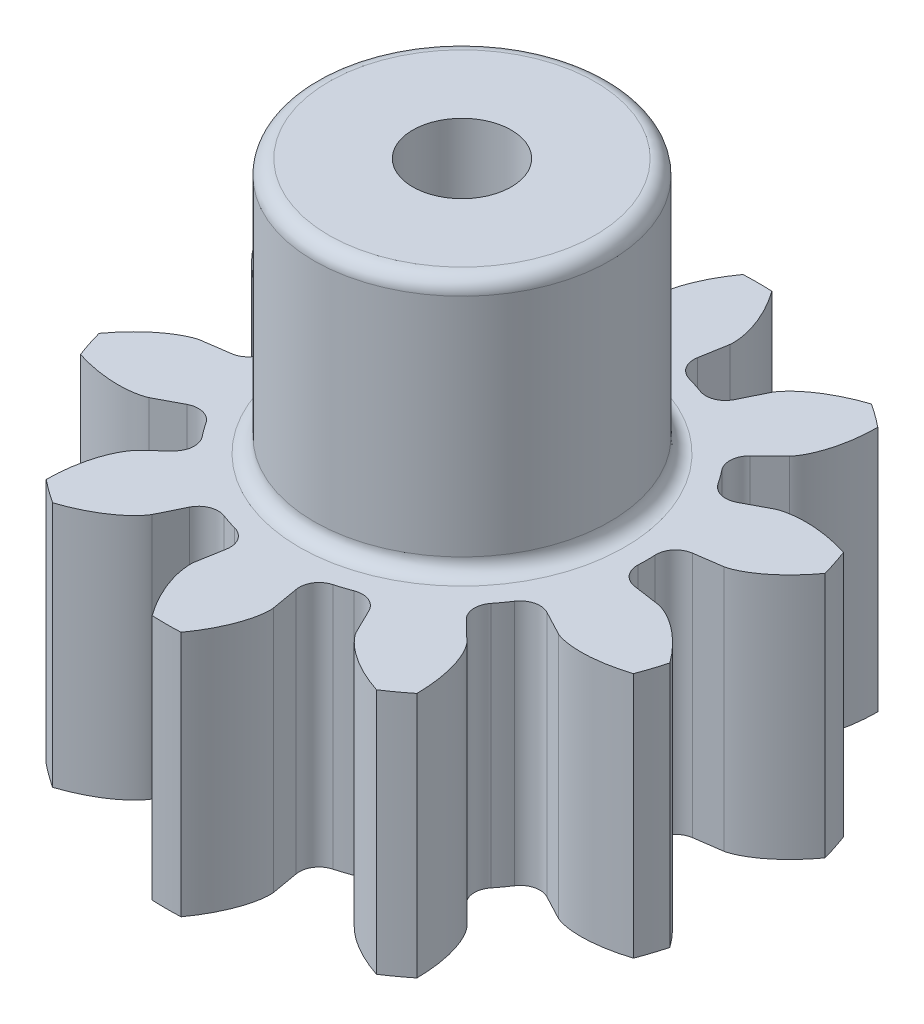
SolidWorks part; units mm, degrees
ref_plane "Front Plane" through (0, 0, 0) normal (0, 0, 1) x (1, 0, 0)
ref_plane "Top Plane" through (0, 0, 0) normal (0, 1, 0) x (1, 0, 0)
ref_plane "Right Plane" through (0, 0, 0) normal (1, 0, 0) x (0, 0, -1)
sketch "Sketch2" plane through (0, 0, 0) normal (0, 1, 0) x (1, 0, 0)
  circle A0 centre (0, 0) radius 15.24
  dimension "D1" = 30.48
extrude "Boss-Extrude1" add sketch "Sketch2" along normal blind 12.7
sketch "Sketch3" plane through (0, 0, 0) normal (0, -1, 0) x (-1, 0, 0)
  line L0 (0, 0) -> (11.8137, -1.691) construction
  line L1 (0, 0) -> (11.8137, 1.691) construction
  line L2 (11.8137, -1.691) -> (9.4289, -1.3497)
  line L3 (11.8137, 1.691) -> (9.4289, 1.3497)
  circle A0 centre (0, 0) radius 15.24
  circle A1 centre (0, 0) radius 12.7
  circle A2 centre (0, 0) radius 11.938
  circle A3 centre (0, 0) radius 9.525
  arc A4 (14.7073, 3.9942) -> (14.7073, -3.9942) centre (0, 0) cw
  arc A5 (9.4289, 1.3497) -> (9.4289, -1.3497) centre (0, 0) cw
  spline S0 degree 4 poles (11.8137, 1.691) (11.8192, 1.6919) (11.8345, 1.6947) (11.8634, 1.701) (11.9102, 1.7129) (11.9692, 1.7305) (12.0448, 1.7558) (12.1329, 1.789) (12.2286, 1.829) (12.3315, 1.8763) (12.433, 1.9267) (12.5329, 1.9801) (12.6314, 2.036) (12.7494, 2.1069) (12.8888, 2.1963) (13.0487, 2.3071) (13.2263, 2.4402) (13.4031, 2.5835) (13.5735, 2.7307) (13.7413, 2.8866) (13.9005, 3.0423) (14.0612, 3.2111) (14.2071, 3.3705) (14.3651, 3.5565) (14.4911, 3.7088) (14.6511, 3.9175) (14.7439, 4.0431) (14.8502, 4.1926) (14.8963, 4.2604) (14.9247, 4.3021) knots 0 0 0 0 0 0.005377 0.015084 0.028532 0.04661 0.064855 0.092111 0.119476 0.146842 0.174209 0.201575 0.228941 0.256307 0.307035 0.361767 0.4165 0.471232 0.525964 0.580697 0.635429 0.690161 0.744894 0.799626 0.854358 0.909091 0.954545 1 1 1 1 1 construction
  spline S1 degree 4 poles (11.8137, 1.691) (11.8192, 1.6919) (11.8345, 1.6947) (11.8634, 1.701) (11.9102, 1.7129) (11.9692, 1.7305) (12.0448, 1.7558) (12.1329, 1.789) (12.2286, 1.829) (12.3315, 1.8763) (12.433, 1.9267) (12.5329, 1.9801) (12.6314, 2.036) (12.7494, 2.1069) (12.8888, 2.1963) (13.0487, 2.3071) (13.2263, 2.4402) (13.4031, 2.5835) (13.5735, 2.7307) (13.7413, 2.8866) (13.9005, 3.0423) (14.0612, 3.2111) (14.2071, 3.3705) (14.3651, 3.5565) (14.4911, 3.7088) (14.6164, 3.8723) (14.6768, 3.9527) (14.7073, 3.9942) knots 0 0 0 0 0 0.005377 0.015084 0.028532 0.04661 0.064855 0.092111 0.119476 0.146842 0.174209 0.201575 0.228941 0.256307 0.307035 0.361767 0.4165 0.471232 0.525964 0.580697 0.635429 0.690161 0.744894 0.799626 0.854358 0.909091 0.909091 0.909091 0.909091 0.909091
  spline S2 degree 4 poles (11.8137, -1.691) (11.8192, -1.6919) (11.8345, -1.6947) (11.8634, -1.701) (11.9102, -1.7129) (11.9692, -1.7305) (12.0448, -1.7558) (12.1329, -1.789) (12.2286, -1.829) (12.3315, -1.8763) (12.433, -1.9267) (12.5329, -1.9801) (12.6314, -2.036) (12.7494, -2.1069) (12.8888, -2.1963) (13.0487, -2.3071) (13.2263, -2.4402) (13.4031, -2.5835) (13.5735, -2.7307) (13.7413, -2.8866) (13.9005, -3.0423) (14.0612, -3.2111) (14.2071, -3.3705) (14.3651, -3.5565) (14.4911, -3.7088) (14.6511, -3.9175) (14.7439, -4.0431) (14.8502, -4.1926) (14.8963, -4.2604) (14.9247, -4.3021) knots 0 0 0 0 0 0.005377 0.015084 0.028532 0.04661 0.064855 0.092111 0.119476 0.146842 0.174209 0.201575 0.228941 0.256307 0.307035 0.361767 0.4165 0.471232 0.525964 0.580697 0.635429 0.690161 0.744894 0.799626 0.854358 0.909091 0.954545 1 1 1 1 1 construction
  spline S3 degree 4 poles (11.8137, -1.691) (11.8192, -1.6919) (11.8345, -1.6947) (11.8634, -1.701) (11.9102, -1.7129) (11.9692, -1.7305) (12.0448, -1.7558) (12.1329, -1.789) (12.2286, -1.829) (12.3315, -1.8763) (12.433, -1.9267) (12.5329, -1.9801) (12.6314, -2.036) (12.7494, -2.1069) (12.8888, -2.1963) (13.0487, -2.3071) (13.2263, -2.4402) (13.4031, -2.5835) (13.5735, -2.7307) (13.7413, -2.8866) (13.9005, -3.0423) (14.0612, -3.2111) (14.2071, -3.3705) (14.3651, -3.5565) (14.4911, -3.7088) (14.6164, -3.8723) (14.6768, -3.9527) (14.7073, -3.9942) knots 0 0 0 0 0 0.005377 0.015084 0.028532 0.04661 0.064855 0.092111 0.119476 0.146842 0.174209 0.201575 0.228941 0.256307 0.307035 0.361767 0.4165 0.471232 0.525964 0.580697 0.635429 0.690161 0.744894 0.799626 0.854358 0.909091 0.909091 0.909091 0.909091 0.909091
  circle M5 centre (0, 0) radius 15.24
  dimension "D1" = 30.48
  dimension "D2" = 25.4
  dimension "D3" = 23.876
  dimension "D4" = 19.05
extrude "Cut-Extrude1" cut sketch "Sketch3" against normal through all contours A1 S3 S1 M5 | A2 S3 A1 S1 | L2 S3 A2 S1 L3 A3 region at (-10.7404, 0, 0) region at (-12.2842, 0, 0) region at (-14.0094, 0, 0)
fillet "Fillet1" radius 1.016 2 edges at (-9.4289, 6.35, -1.3497) (-9.4289, 6.35, 1.3497)
pattern_circular "CirPattern1" count 10 over 360 about axis through (0, 0, 0) along (0, 1, 0) of "Fillet1", "Cut-Extrude1"
sketch "Sketch4" plane through (0, 12.7, 0) normal (0, 1, 0) x (1, 0, 0)
  circle A0 centre (0, 0) radius 2.54
  circle A1 centre (0, 0) radius 7.62
  dimension "D1" = 5.08
  dimension "D2" = 15.24
extrude "Boss-Extrude2" add sketch "Sketch4" along normal blind 13.16
sketch "Sketch5" plane through (0, 12.7, 0) normal (0, 1, 0) x (1, 0, 0)
  circle A0 centre (0, 0) radius 2.525
extrude "Cut-Extrude2" cut sketch "Sketch5" against normal through all
fillet "Fillet2" radius 0.762 2 edges at (0, 25.86, 7.62) (0, 12.7, 7.62)
equation "\"DiametralPitch\"= 10"
equation "\"NumTeeth\"= 10"
equation "\"PressureAngle\"= 20deg"
equation "\"Addendum\"= 1 / \"DiametralPitch\""
equation "\"Dedendum\"= 1.25 / \"DiametralPitch\""
equation "\"WorkingDepth\"= 2 / \"DiametralPitch\""
equation "\"WholeDepth\"= 2.25 / \"DiametralPitch\""
equation "\"Clearance\"= 0.3 / \"DiametralPitch\""
equation "\"ToothThickness\"= 1.5708 / \"DiametralPitch\""
equation "\"CircularPitch\"= pi / \"DiametralPitch\""
equation "\"PitchCircle\"= \"NumTeeth\" / \"DiametralPitch\""
equation "\"OutsideDiameter\"= ( \"NumTeeth\" + 2 ) / \"DiametralPitch\""
equation "\"Fillet\"= \"Clearance\" * cos ( \"PressureAngle\" ) * tan ( ( 90 + \"PressureAngle\" ) / 2 )"
equation "\"AddendumCircle\"= \"PitchCircle\" + ( 2 * \"Addendum\" )"
equation "\"DedendumCircle\"= \"PitchCircle\" - ( 2 * \"Dedendum\" )"
equation "\"BaseCircle\"= \"PitchCircle\" * cos ( \"PressureAngle\" )"
equation "\"PitchAngle\"= 360deg / \"NumTeeth\""
equation "\"Alpha\"= sqr ( \"PitchCircle\" ^ 2 - \"BaseCircle\" ^ 2 ) / \"BaseCircle\" * 180 / PI - \"PressureAngle\""
equation "\"Beta\"= ( \"PitchAngle\" / 4 - \"Alpha\" )"
equation "\"Phi\"= sqr ( ( \"AddendumCircle\" / 2 ) ^ 2 - ( \"BaseCircle\" / 2 ) ^ 2 ) / ( \"BaseCircle\" / 2 )"
